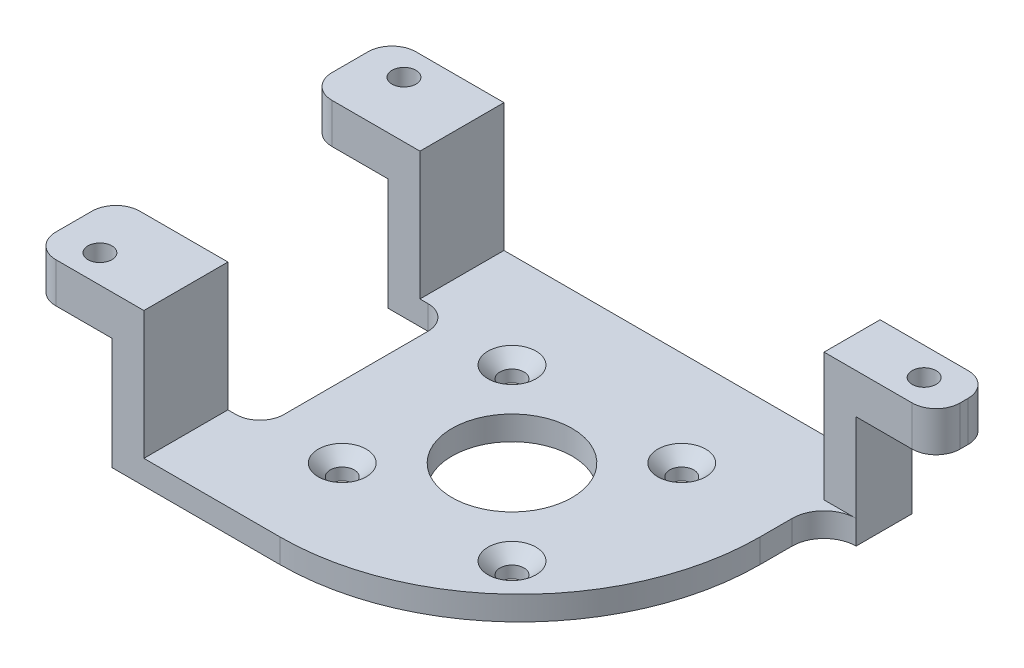
SolidWorks part; units mm, degrees
material "6061 合金"
ref_plane "前视基准面" through (0, 0, 0) normal (0, 0, 1) x (1, 0, 0)
ref_plane "上视基准面" through (0, 0, 0) normal (0, 1, 0) x (1, 0, 0)
ref_plane "右视基准面" through (0, 0, 0) normal (1, 0, 0) x (0, 0, -1)
sketch "草图1" plane through (0, 0, 0) normal (0, 1, 0) x (1, 0, 0)
  line L1 (-37.5, 22.5) -> (37.5, 22.5)
  line L2 (-37.5, 22.5) -> (-37.5, -22.5)
  line L3 (-37.5, -22.5) -> (37.5, -22.5)
  line L4 (37.5, 22.5) -> (37.5, -22.5)
  line L5 (-37.5, 22.5) -> (37.5, -22.5) construction
  line L6 (-37.5, -22.5) -> (37.5, 22.5) construction
  point P0 (0, 0)
  dimension "D1" = 45
  dimension "D2" = 75
extrude "凸台-拉伸1" add sketch "草图1" along normal blind 19
sketch "草图2" plane through (0, 0, 0) normal (0, -1, 0) x (1, 0, 0)
  line L0 (37.5, -22.5) -> (-37.5, -22.5) construction
  line L1 (-37.5, 22.5) -> (-27.5, 22.5)
  line L2 (-37.5, 22.5) -> (-37.5, -22.5)
  line L3 (-37.5, -22.5) -> (-27.5, -22.5)
  line L4 (-27.5, 22.5) -> (-27.5, -22.5)
  line L5 (0, -22.5) -> (0, 22.5) construction
  line L6 (-37.5, 22.5) -> (37.5, 22.5) construction
  line L7 (37.5, -22.5) -> (27.5, -22.5)
  line L8 (27.5, 22.5) -> (27.5, -22.5)
  line L9 (37.5, 22.5) -> (27.5, 22.5)
  line L10 (37.5, 22.5) -> (37.5, -22.5)
  dimension "D1" = 10
extrude "切除-拉伸1" cut sketch "草图2" against normal blind 14
sketch "草图3" plane through (0, 19, 0) normal (0, 1, 0) x (1, 0, 0)
  line L0 (37.5, 22.5) -> (-37.5, 22.5) construction
  line L1 (-23.5, -22.5) -> (23.5, -22.5)
  line L2 (-23.5, -22.5) -> (-23.5, 22.5)
  line L3 (-23.5, 22.5) -> (23.5, 22.5)
  line L4 (23.5, -22.5) -> (23.5, 22.5)
  line L5 (-23.5, -22.5) -> (23.5, 22.5) construction
  line L6 (-23.5, 22.5) -> (23.5, -22.5) construction
  point P0 (0, 0)
  dimension "D1" = 47
extrude "切除-拉伸2" cut sketch "草图3" against normal blind 16
sketch "草图4" plane through (0, 0, 0) normal (0, -1, 0) x (1, 0, 0)
  line L0 (0, 15) -> (0, 0) construction
  line L1 (0, 0) -> (10.6066, 10.6066) construction
  circle A0 centre (0, 0) radius 15 construction
  circle A1 centre (10.6066, 10.6066) radius 1.5
  circle A2 centre (10.6066, -10.6066) radius 1.5
  circle A3 centre (-10.6066, -10.6066) radius 1.5
  circle A4 centre (-10.6066, 10.6066) radius 1.5
  circle A5 centre (0, 0) radius 7.5
  point P15 (0, 0)
  dimension "D1" = 30
  dimension "D3" = 3
  dimension "D5" = 15
  dimension "D2" = 45
  dimension "D4" = 4
extrude "切除-拉伸3" cut sketch "草图4" against normal through all
sketch "草图5" plane through (0, 19, 0) normal (0, 1, 0) x (1, 0, 0)
  line L5 (37.5, -22.5) -> (37.5, 22.5) construction
  line L6 (23.5, -22.5) -> (37.5, -22.5)
  line L7 (23.5, -22.5) -> (23.5, 15.5)
  line L8 (23.5, 15.5) -> (37.5, 15.5)
  line L9 (37.5, -22.5) -> (37.5, 15.5)
  dimension "D2" = 38
extrude "切除-拉伸4" cut sketch "草图5" against normal through all
fillet "圆角1" radius 30 1 edges at (23.5, 1.5, 22.5)
chamfer "倒角1" distance 1.5 angle 45 4 edges at (-10.6066, 3, 9.1066) (-10.6066, 3, -12.1066) (10.6066, 3, -12.1066) (10.6066, 3, 9.1066)
sketch "草图8" plane through (0, 0, 0) normal (0, -1, 0) x (1, 0, 0)
  line L0 (0, 0) -> (-37.5, 0) construction
  line L1 (-37.5, 22.5) -> (-37.5, -22.5) construction
  line L3 (-19.5, -12) -> (-55.5, -12)
  line L4 (-19.5, -12) -> (-19.5, 12)
  line L5 (-19.5, 12) -> (-55.5, 12)
  line L6 (-55.5, -12) -> (-55.5, 12)
  line L7 (-19.5, -12) -> (-55.5, 12) construction
  line L8 (-19.5, 12) -> (-55.5, -12) construction
  dimension "D1" = 24
  dimension "D2" = 18
extrude "切除-拉伸6" cut sketch "草图8" against normal through all
fillet "圆角2" radius 3 2 edges at (-19.5, 1.5, -12) (-19.5, 1.5, 12)
sketch "草图9" plane through (0, 14, 0) normal (0, -1, 0) x (1, 0, 0)
  line L0 (27.5, -22.5) -> (37.5, -22.5) construction
  line L1 (32.5, -19) -> (-32.5, -19) construction
  line L2 (32.5, -19) -> (32.5, 19) construction
  line L3 (32.5, 19) -> (-32.5, 19) construction
  line L4 (-32.5, -19) -> (-32.5, 19) construction
  line L5 (32.5, -19) -> (-32.5, 19) construction
  line L6 (32.5, 19) -> (-32.5, -19) construction
  line L7 (37.5, -22.5) -> (37.5, -15.5) construction
  circle A0 centre (32.5, -19) radius 1.5
  circle A1 centre (-32.5, -19) radius 1.5
  circle A2 centre (-32.5, 19) radius 1.5
  point P0 (0, 0)
  dimension "D3" = 3
  dimension "D4" = 3
  dimension "D5" = 3
  dimension "D1" = 3.5
  dimension "D2" = 5
extrude "切除-拉伸7" cut sketch "草图9" against normal through all
fillet "圆角3" radius 3 6 edges at (37.5, 16.5, -15.5) (37.5, 16.5, -22.5) (-37.5, 16.5, -12) (-37.5, 16.5, -22.5) (-37.5, 16.5, 22.5) (-37.5, 16.5, 12)
fillet "圆角4" radius 4 1 edges at (23.5, 1.5, -15.5)
